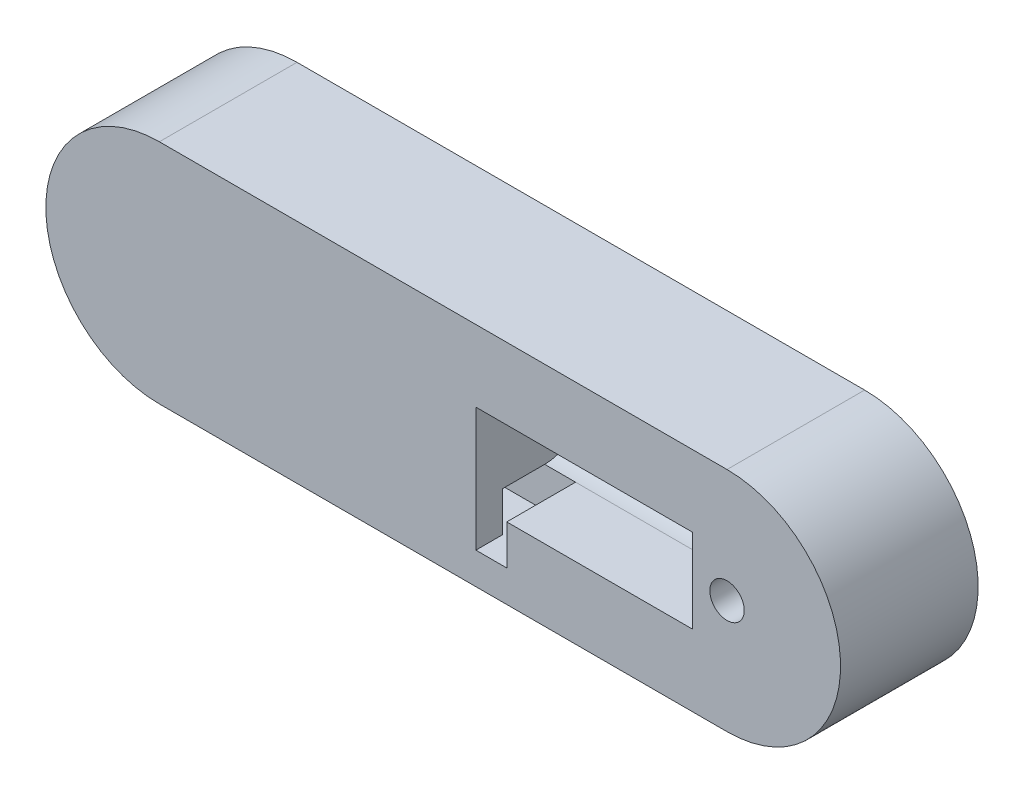
SolidWorks part; units mm, degrees
note: The reader was unsure of these and kept them because the rebuilt part matched: shared geometry of "Croquis1<4>".
ref_plane "Alzado" through (0, 0, 0) normal (0, 0, 1) x (1, 0, 0)
ref_plane "Planta" through (0, 0, 0) normal (0, 1, 0) x (1, 0, 0)
ref_plane "Vista lateral" through (0, 0, 0) normal (1, 0, 0) x (0, 0, -1)
sketch "Croquis1" plane through (0, 0, 0) normal (0, 0, 1) x (1, 0, 0)
  line L0 (-43.0271, -33) -> (121.9729, -33)
  line L1 (-43.0271, 33) -> (121.9729, 33)
  line L2 (-41.5099, 1.3031) -> (-41.5099, -1.3031)
  circle A0 centre (-43.0271, 0) radius 33
  circle A1 centre (121.9729, 0) radius 33
  circle A2 centre (-43.0271, 0) radius 2
  circle A3 centre (121.9729, 0) radius 5
  dimension "D2" = 4
  dimension "D3" = 10
  dimension "D4" = 66
  dimension "D1" = 165
extrude "Saliente-Extruir1" add sketch "Croquis1" along normal blind 40 contours A0 L0 A2 | A1 L1 A0 L0 | L1 A1 A3 | A2 | L2 A2
extrude "Cortar-Extruir2" cut sketch "Croquis1<4>" along normal blind 10 contours L2 A2
sketch "Croquis1<4>" plane through (0, 0, 0) normal (0, 0, 1) x (1, 0, 0) same geometry as "Croquis1"
sketch "Croquis5" plane through (0, 0, 40) normal (0, 0, 1) x (1, 0, 0)
  line L0 (57.9485, -23.8) -> (57.9485, -12.2)
  line L1 (57.9485, -12.2) -> (111.9729, -12.2)
  line L9 (48.9729, 12.2) -> (48.9729, -23.8)
  line L10 (111.9729, -12.2) -> (111.9729, 12.2)
  line L13 (48.9729, -23.8) -> (57.9485, -23.8)
  line L14 (111.9729, 12.2) -> (48.9729, 12.2)
  arc A0 (121.9729, -33) -> (121.9729, 33) centre (121.9729, 0) ccw construction
  arc A1 (121.9729, -33) -> (121.9729, 33) centre (121.9729, 0) ccw
  circle A2 centre (121.9729, 0) radius 5 construction
  circle A3 centre (121.9729, 0) radius 5
  point P2 (111.9729, 0)
  dimension "D2" = 10
  dimension "D3" = 63
  dimension "D4" = 24.4
  dimension "D1" = 11.6
extrude "Cortar-Extruir4" cut sketch "Croquis5" against normal blind 20 contours L10 L14 L9 L13 L0 L1
ref_plane "Plano2" through (48.9729, 0, 0) normal (1, 0, 0) x (0, 0, -1)
sketch "Croquis6" plane through (48.9729, 0, 0) normal (1, 0, 0) x (0, 0, -1)
  line L0 (-20, 12.2) -> (-40, 12.2)
  line L1 (-20, -12.2) -> (-40, -12.2)
  line L2 (-20, -23.8) -> (-20, -12.2)
  line L4 (-40, 12.2) -> (-40, -23.8)
  line L6 (-20, -23.8) -> (-20, 12.2)
  line L7 (-20, 12.2) -> (-40, 12.2)
  line L8 (-40, 12.2) -> (-40, -23.8)
  line L11 (-20, 12.2) -> (-40, 12.2)
  line L16 (0, -33) -> (0, 33)
  line L17 (0, 33) -> (-40, 33)
  line L18 (-40, 33) -> (-40, -33)
  line L19 (-40, -33) -> (0, -33)
  line L20 (0, -33) -> (0, 33)
  line L21 (0, 33) -> (-40, 33)
  line L22 (-40, 33) -> (-40, -33)
  line L23 (-40, -33) -> (0, -33)
  line L24 (-40, -23.8) -> (-20, -23.8)
  line L25 (-40, -23.8) -> (-20, -23.8)
  circle A0 centre (-20, 0) radius 12.2
  dimension "D2" = 24.4
  dimension "D3" = 0
  dimension "D1" = 0
extrude "Cortar-Extruir6" cut sketch "Croquis6" along direction (1, 0, 0) on the side of the normal up to surface (63 mm away) contours A0 | A0 L0 L8 L1
sketch "Croquis7" plane through (111.9729, 0, 0) normal (-1, 0, 0) x (0, 0, 1)
  line L1 (40, -12.2) -> (40.0638, -12.2)
  line L3 (20, -12.2) -> (7.8, -12.2)
  line L4 (20, -12.2) -> (20, 12.2) construction
  line L5 (20, 12.2) -> (7.8, 12.2)
  line L9 (40, 12.2) -> (40.0638, 12.2)
  line L11 (7.8, -12.2) -> (7.8, 12.2)
  line L12 (40, -12.2) -> (40, 12.2)
  line L13 (40, 12.2) -> (20, 12.2)
  line L16 (20, -12.2) -> (40, -12.2)
  line L17 (40, -12.2) -> (40, 12.2)
  line L22 (40, 12.2) -> (20, 12.2)
  line L26 (7.8, -12.2) -> (32.2, -12.2)
  line L27 (7.8, -12.2) -> (7.8, 12.2)
  line L28 (7.8, 12.2) -> (32.2, 12.2)
  line L29 (32.2, -12.2) -> (32.2, 12.2)
  line L34 (20, -12.2) -> (40, -12.2)
  circle A0 centre (20, 0) radius 12.2 construction
  arc A1 (20, 12.2) -> (20, -12.2) centre (20, 0) ccw
  arc A5 (20, 12.2) -> (20, -12.2) centre (20, 0) ccw
  dimension "D1" = 0
extrude "Cortar-Extruir9" cut sketch "Croquis7" against normal blind 30
sketch "Croquis8" plane through (48.9729, 0, 0) normal (1, 0, 0) x (0, 0, -1)
  line L0 (-32.2, -12.2) -> (-32.2, -23.8)
  line L4 (-32.2, -12.2) -> (-32.2, 12.2)
  line L5 (-40, -12.2) -> (-32.2, -12.2)
  line L6 (-40, 12.2) -> (-40, -12.2)
  line L7 (-32.2, 12.2) -> (-40, 12.2)
  line L8 (-40, -12.2) -> (-40, -23.8)
  line L9 (-20, -12.2) -> (-40, -12.2)
  line L10 (-20, -23.8) -> (-20, -12.2)
  line L11 (-40, -23.8) -> (-20, -23.8)
  line L12 (-40, -12.2) -> (-40, -23.8)
  line L13 (-20, -12.2) -> (-32.2, -12.2)
  line L14 (-20, -23.8) -> (-20, -12.2)
  line L15 (-40, -23.8) -> (-20, -23.8)
  line L18 (-40, 12.2) -> (-40, -12.2)
  line L19 (-32.2, 12.2) -> (-40, 12.2)
  line M10 (-40, -23.8) -> (-20, -23.8)
  line M11 (-20, -23.8) -> (-20, -12.2)
  dimension "D1" = 0
  dimension "D2" = 0
extrude "Cortar-Extruir10" cut sketch "Croquis8" against normal blind 85 contours L13 L0 M11 M10
sketch "Croquis9" plane through (0, 0, 0) normal (0, 0, -1) x (-1, 0, 0)
  line L0 (24.4271, -23.8) -> (24.4271, -12.2)
  line L8 (-48.9729, -12.2) -> (-48.9729, -23.8)
  line L9 (-48.9729, -23.8) -> (36.0271, -23.8)
  line L10 (36.0271, -23.8) -> (36.0271, -12.2)
  line L11 (36.0271, -12.2) -> (-48.9729, -12.2)
  line L13 (24.4271, -23.8) -> (36.0271, -23.8)
  line L14 (36.0271, -23.8) -> (36.0271, -12.2)
  line L15 (36.0271, -12.2) -> (24.4271, -12.2)
  dimension "D2" = 0
extrude "Cortar-Extruir11" cut sketch "Croquis9" against normal up to next
chamfer "Chaflán1" distance 10 angle 45 1 edges at (-36.0271, -18, 0)
